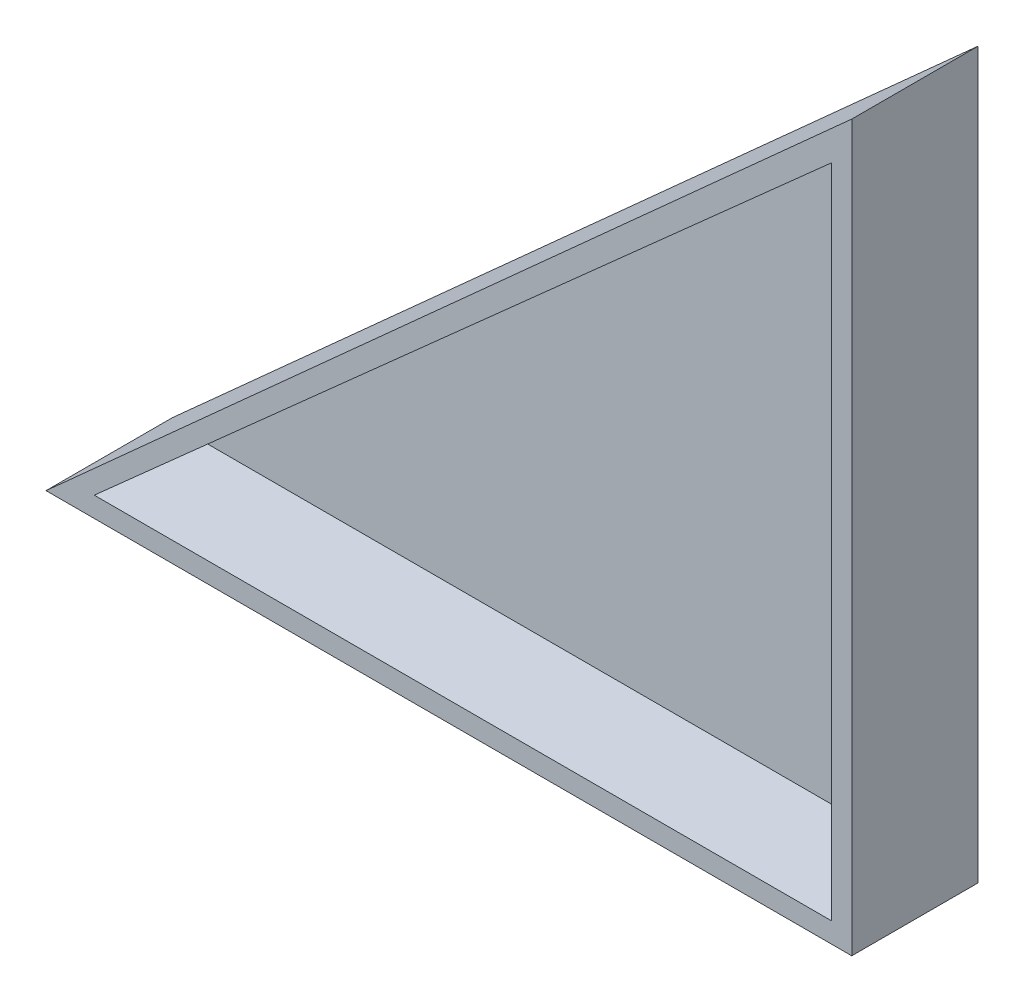
SolidWorks part; units mm, degrees
ref_plane "Front Plane" through (0, 0, 0) normal (0, 0, 1) x (1, 0, 0)
ref_plane "Top Plane" through (0, 0, 0) normal (0, 1, 0) x (1, 0, 0)
ref_plane "Right Plane" through (0, 0, 0) normal (1, 0, 0) x (0, 0, -1)
sketch "Sketch1" plane through (0, 0, 0) normal (0, 0, 1) x (1, 0, 0)
  line L0 (33.2174, 54.3487) -> (33.2174, 13.0737)
  line L1 (33.2174, 13.0737) -> (-13.1376, 13.0737)
  line L2 (33.2174, 54.3487) -> (-13.1376, 13.0737)
  line L6 (34.4874, 57.3647) -> (34.4874, 11.8037)
  line L7 (34.4874, 11.8037) -> (-16.1718, 11.8037)
  line L8 (34.4874, 57.3647) -> (-16.1718, 11.8037)
  point P2 (0, 0)
  point P4 (0, 0)
  point P5 (0, 0)
  point P6 (0, 0)
extrude "Boss-Extrude2" add sketch "Sketch1" along normal blind 1.5875 contours L2 L1 L0
extrude "Boss-Extrude3" add sketch "Sketch1<5>" along normal blind 7.9375
sketch "Sketch1<5>" plane through (0, 0, 0) normal (0, 0, 1) x (1, 0, 0) same geometry as "Sketch1"
ref_plane "Plane1" through (33.2174, 54.3487, 1.5875) normal (0, -1, 0) x (-1, 0, 0)
sketch "Sketch2" plane through (33.2174, 54.3487, 1.5875) normal (0, -1, 0) x (1, 0, 0)
